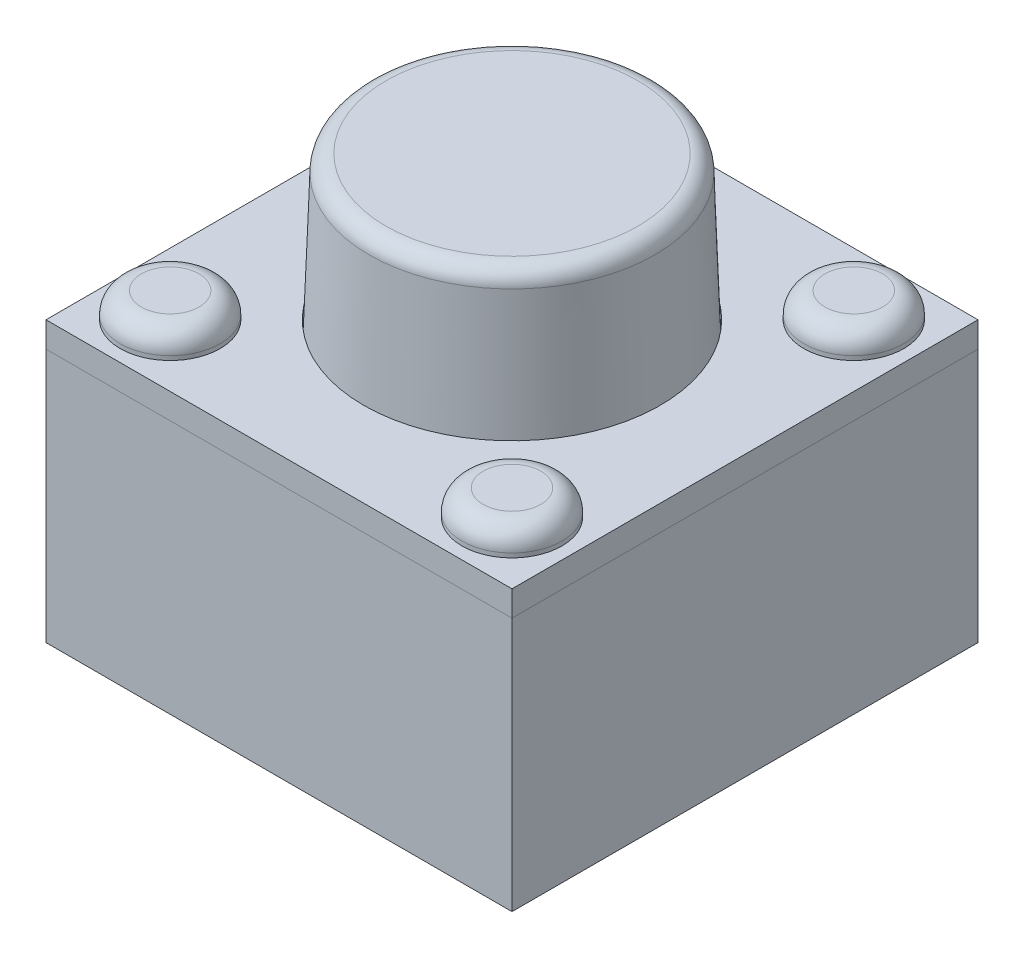
SolidWorks part; units mm, degrees
ref_plane "Front Plane" through (0, 0, 0) normal (0, 0, 1) x (1, 0, 0)
ref_plane "Top Plane" through (0, 0, 0) normal (0, 1, 0) x (1, 0, 0)
ref_plane "Right Plane" through (0, 0, 0) normal (1, 0, 0) x (0, 0, -1)
sketch "Sketch1" plane through (0, 0, 0) normal (0, 1, 0) x (1, 0, 0)
  line L1 (-2.75, 2.75) -> (2.75, 2.75)
  line L2 (-2.75, 2.75) -> (-2.75, -2.75)
  line L3 (-2.75, -2.75) -> (2.75, -2.75)
  line L4 (2.75, 2.75) -> (2.75, -2.75)
  line L5 (-2.75, 2.75) -> (2.75, -2.75) construction
  line L6 (-2.75, -2.75) -> (2.75, 2.75) construction
  point P0 (0, 0)
  dimension "D1" = 5.5
extrude "Boss-Extrude1" add sketch "Sketch1" along normal blind 3
sketch "Sketch2" plane through (0, 3, 0) normal (0, 1, 0) x (1, 0, 0)
  line L0 (-2.75, 2.75) -> (2.75, -2.75) construction
  line L1 (-2.75, 2.75) -> (-2.75, -2.75) construction
  line L2 (2.75, 2.75) -> (-2.75, 2.75) construction
  line L3 (2.75, -2.75) -> (2.75, 2.75) construction
  line L4 (-2.75, -2.75) -> (2.75, -2.75) construction
  line L5 (-2.75, 2.75) -> (-2.75, -2.75)
  line L6 (2.75, 2.75) -> (-2.75, 2.75)
  line L7 (2.75, -2.75) -> (2.75, 2.75)
  line L8 (-2.75, -2.75) -> (2.75, -2.75)
  circle A0 centre (0, 0) radius 1.75
  circle A1 centre (-2.0172, 2.0172) radius 0.59
  circle A2 centre (2.0172, 2.0172) radius 0.59
  circle A3 centre (2.0172, -2.0172) radius 0.59
  circle A4 centre (-2.0172, -2.0172) radius 0.59
  point P15 (0, 0)
  dimension "D1" = 3.5
  dimension "D2" = 1.18
  dimension "D3" = 4
extrude "Boss-Extrude2" add sketch "Sketch2" along normal blind 0.3 separate body
extrude "Boss-Extrude3" add sketch "Sketch2<2>" along normal blind 0.6 contours A1 | A2 | A3 | A4 region at (-2.0172, 3, -2.0172) region at (2.0172, 3, -2.0172) region at (2.0172, 3, 2.0172) region at (-2.0172, 3, 2.0172)
sketch "Sketch2<2>" plane through (0, 3, 0) normal (0, 1, 0) x (1, 0, 0) same geometry as "Sketch2"
extrude "Boss-Extrude4" add sketch "Sketch2<3>" along normal blind 2 draft 2 separate body contours A0 region at (0, 3, 0)
sketch "Sketch2<3>" plane through (0, 3, 0) normal (0, 1, 0) x (1, 0, 0) same geometry as "Sketch2"
fillet "Fillet1" radius 0.25 4 edges at (2.0172, 3.6, -1.4272) (2.0172, 3.6, 2.6072) (-2.0172, 3.6, 2.6072) (-2.0172, 3.6, -1.4272)
fillet "Fillet2" radius 0.2 1 edges at (0, 5, 1.6802)
